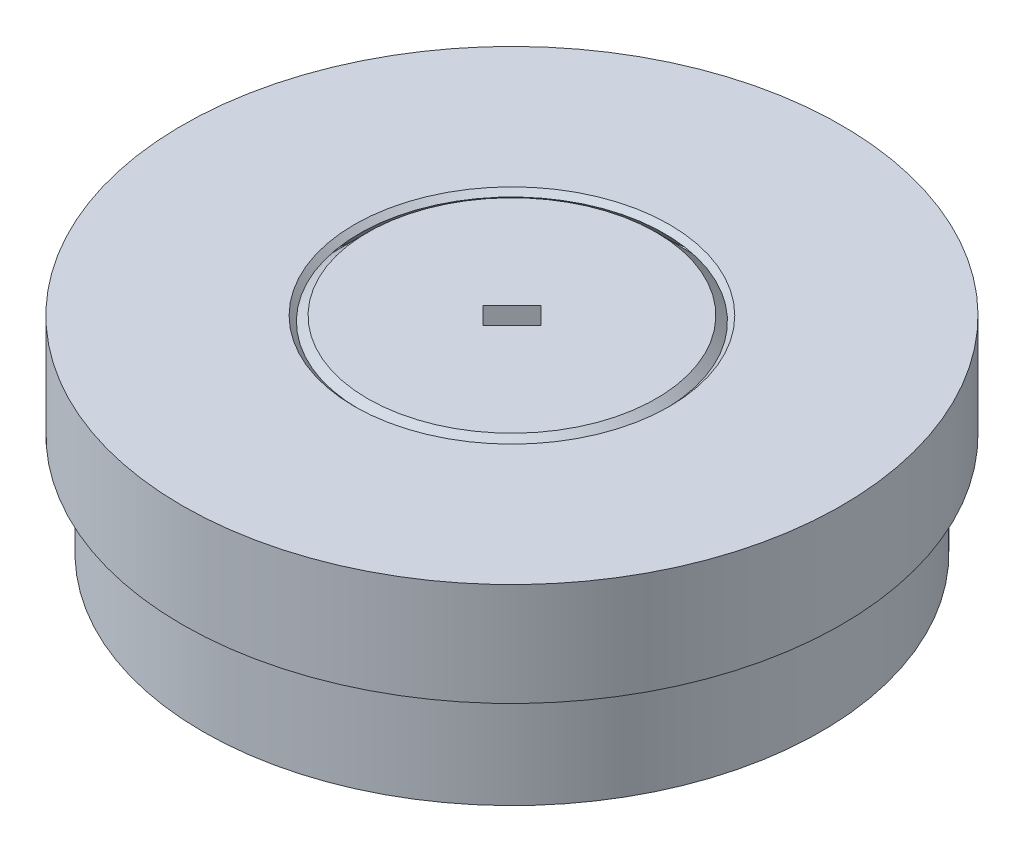
SolidWorks part; units mm, degrees
ref_plane "Front Plane" through (0, 0, 0) normal (0, 0, 1) x (1, 0, 0)
ref_plane "Top Plane" through (0, 0, 0) normal (0, 1, 0) x (1, 0, 0)
ref_plane "Right Plane" through (0, 0, 0) normal (1, 0, 0) x (0, 0, -1)
sketch "Sketch3" plane through (0, 0, 0) normal (0, 1, 0) x (1, 0, 0)
  line L0 (0, 0) -> (0, 14) construction
  line L1 (0, 11) -> (0, 14)
  line L2 (6.4656, 8.8992) -> (8.229, 11.3262)
  line L3 (10.4616, 3.3992) -> (13.3148, 4.3262)
  line L4 (10.4616, -3.3992) -> (13.3148, -4.3262)
  line L5 (6.4656, -8.8992) -> (8.229, -11.3262)
  line L6 (0, -11) -> (0, -14)
  line L7 (-6.4656, -8.8992) -> (-8.229, -11.3262)
  line L8 (-10.4616, -3.3992) -> (-13.3148, -4.3262)
  line L9 (-10.4616, 3.3992) -> (-13.3148, 4.3262)
  line L10 (-6.4656, 8.8992) -> (-8.229, 11.3262)
  line L12 (2, 2) -> (-2, 2)
  line L13 (2, 2) -> (2, -2)
  line L14 (2, -2) -> (-2, -2)
  line L15 (-2, 2) -> (-2, -2)
  line L16 (0, -2) -> (0, 2) construction
  line L17 (2, 0) -> (-2, 0) construction
  circle A0 centre (0, 0) radius 15
  circle A1 centre (0, 0) radius 14 construction
  spline S0 degree 4 poles (-0.6778, 10.6763) (-0.6286, 10.7014) (-0.5336, 10.7495) (-0.4182, 10.8106) (-0.084, 10.9641) (0.0577, 11.0264) (0.4379, 11.1818) (0.6637, 11.2619) (0.971, 11.3685) (1.234, 11.4472) (1.5272, 11.5305) (1.8056, 11.5989) (2.0959, 11.6642) (2.3817, 11.7192) (2.6725, 11.7684) (2.9623, 11.8092) (3.2542, 11.8431) (3.5945, 11.8737) (4.009, 11.8986) (4.4979, 11.9088) (4.9859, 11.897) (5.4262, 11.8684) (5.7898, 11.8338) (6.0839, 11.7981) (6.4416, 11.7478) (6.8131, 11.6815) (7.1561, 11.6125) (7.5364, 11.5205) (7.7792, 11.459) (8.1801, 11.3427) (8.3369, 11.2932) (8.7269, 11.165) (8.8594, 11.1137) (8.9726, 11.0725) (9.0307, 11.0511) knots 0 0 0 0 0 0.018755 0.037509 0.074516 0.103872 0.133229 0.162585 0.191942 0.221299 0.250655 0.280012 0.309368 0.338725 0.368082 0.397438 0.426795 0.456151 0.504872 0.563586 0.622299 0.651656 0.681012 0.710369 0.739725 0.798439 0.827795 0.857152 0.886508 0.915865 0.957933 0.978966 1 1 1 1 1 construction
  spline S1 degree 4 poles (0, 11) (0.0566, 11.0246) (0.1702, 11.0724) (0.4379, 11.1818) (0.6637, 11.2619) (0.971, 11.3685) (1.234, 11.4472) (1.5272, 11.5305) (1.8056, 11.5989) (2.0959, 11.6642) (2.3817, 11.7192) (2.6725, 11.7684) (2.9623, 11.8092) (3.2542, 11.8431) (3.5945, 11.8737) (4.009, 11.8986) (4.4979, 11.9088) (4.9859, 11.897) (5.4262, 11.8684) (5.7898, 11.8338) (6.0839, 11.7981) (6.4416, 11.7478) (6.8131, 11.6815) (7.1561, 11.6125) (7.5364, 11.5205) (7.7792, 11.459) (8.0505, 11.3803) (8.17, 11.3445) (8.229, 11.3262) knots 0.074516 0.074516 0.074516 0.074516 0.074516 0.103872 0.133229 0.162585 0.191942 0.221299 0.250655 0.280012 0.309368 0.338725 0.368082 0.397438 0.426795 0.456151 0.504872 0.563586 0.622299 0.651656 0.681012 0.710369 0.739725 0.798439 0.827795 0.857152 0.886508 0.915865 0.915865 0.915865 0.915865 0.915865
  spline S2 degree 4 poles (5.727, 9.0357) (5.7816, 9.0271) (5.8867, 9.0101) (6.016, 8.9918) (6.3766, 8.9195) (6.5279, 8.8866) (6.9268, 8.7889) (7.1565, 8.7209) (7.4678, 8.6266) (7.7268, 8.5357) (8.013, 8.4307) (8.2785, 8.3224) (8.5517, 8.2045) (8.8152, 8.0811) (9.0794, 7.95) (9.3378, 7.8126) (9.5939, 7.6685) (9.8872, 7.4932) (10.2371, 7.2697) (10.6387, 6.9906) (11.0265, 6.6943) (11.3659, 6.4123) (11.6398, 6.1706) (11.8567, 5.9689) (12.1165, 5.7179) (12.3781, 5.4459) (12.6151, 5.1885) (12.8687, 4.8905) (13.029, 4.698) (13.2848, 4.3683) (13.3827, 4.236) (13.6228, 3.9031) (13.6999, 3.7838) (13.7672, 3.6839) (13.8017, 3.6324) knots 0 0 0 0 0 0.018755 0.037509 0.074516 0.103872 0.133229 0.162585 0.191942 0.221299 0.250655 0.280012 0.309368 0.338725 0.368082 0.397438 0.426795 0.456151 0.504872 0.563586 0.622299 0.651656 0.681012 0.710369 0.739725 0.798439 0.827795 0.857152 0.886508 0.915865 0.957933 0.978966 1 1 1 1 1 construction
  spline S3 degree 4 poles (6.4656, 8.8992) (6.5259, 8.8858) (6.6459, 8.8577) (6.9268, 8.7889) (7.1565, 8.7209) (7.4678, 8.6266) (7.7268, 8.5357) (8.013, 8.4307) (8.2785, 8.3224) (8.5517, 8.2045) (8.8152, 8.0811) (9.0794, 7.95) (9.3378, 7.8126) (9.5939, 7.6685) (9.8872, 7.4932) (10.2371, 7.2697) (10.6387, 6.9906) (11.0265, 6.6943) (11.3659, 6.4123) (11.6398, 6.1706) (11.8567, 5.9689) (12.1165, 5.7179) (12.3781, 5.4459) (12.6151, 5.1885) (12.8687, 4.8905) (13.029, 4.698) (13.2021, 4.4749) (13.2778, 4.3756) (13.3148, 4.3262) knots 0.074516 0.074516 0.074516 0.074516 0.074516 0.103872 0.133229 0.162585 0.191942 0.221299 0.250655 0.280012 0.309368 0.338725 0.368082 0.397438 0.426795 0.456151 0.504872 0.563586 0.622299 0.651656 0.681012 0.710369 0.739725 0.798439 0.827795 0.857152 0.886508 0.915865 0.915865 0.915865 0.915865 0.915865
  spline S4 degree 4 poles (9.9443, 3.9438) (9.9834, 3.9047) (10.0585, 3.8292) (10.1522, 3.7384) (10.4015, 3.468) (10.5046, 3.3524) (10.7698, 3.0389) (10.9158, 2.8489) (11.1122, 2.5895) (11.2683, 2.3638) (11.4381, 2.1106) (11.5892, 1.867) (11.7409, 1.6111) (11.8816, 1.3563) (12.0183, 1.095) (12.1466, 0.8319) (12.2691, 0.5648) (12.4033, 0.2506) (12.5551, -0.1359) (12.7158, -0.5977) (12.8555, -1.0654) (12.9643, -1.493) (13.0438, -1.8496) (13.1007, -2.1403) (13.1634, -2.496) (13.2151, -2.8698) (13.2555, -3.2174) (13.2855, -3.6076) (13.3021, -3.8575) (13.3153, -4.2746) (13.3167, -4.4391) (13.3153, -4.8496) (13.3075, -4.9915) (13.3032, -5.1118) (13.3009, -5.1737) knots 0 0 0 0 0 0.018755 0.037509 0.074516 0.103872 0.133229 0.162585 0.191942 0.221299 0.250655 0.280012 0.309368 0.338725 0.368082 0.397438 0.426795 0.456151 0.504872 0.563586 0.622299 0.651656 0.681012 0.710369 0.739725 0.798439 0.827795 0.857152 0.886508 0.915865 0.957933 0.978966 1 1 1 1 1 construction
  spline S5 degree 4 poles (10.4616, 3.3992) (10.5025, 3.3529) (10.583, 3.2597) (10.7698, 3.0389) (10.9158, 2.8489) (11.1122, 2.5895) (11.2683, 2.3638) (11.4381, 2.1106) (11.5892, 1.867) (11.7409, 1.6111) (11.8816, 1.3563) (12.0183, 1.095) (12.1466, 0.8319) (12.2691, 0.5648) (12.4033, 0.2506) (12.5551, -0.1359) (12.7158, -0.5977) (12.8555, -1.0654) (12.9643, -1.493) (13.0438, -1.8496) (13.1007, -2.1403) (13.1634, -2.496) (13.2151, -2.8698) (13.2555, -3.2174) (13.2855, -3.6076) (13.3021, -3.8575) (13.311, -4.1398) (13.3139, -4.2645) (13.3148, -4.3262) knots 0.074516 0.074516 0.074516 0.074516 0.074516 0.103872 0.133229 0.162585 0.191942 0.221299 0.250655 0.280012 0.309368 0.338725 0.368082 0.397438 0.426795 0.456151 0.504872 0.563586 0.622299 0.651656 0.681012 0.710369 0.739725 0.798439 0.827795 0.857152 0.886508 0.915865 0.915865 0.915865 0.915865 0.915865
  spline S6 degree 4 poles (10.3632, -2.6545) (10.3719, -2.7091) (10.3882, -2.8143) (10.4107, -2.9429) (10.4535, -3.3082) (10.4689, -3.4622) (10.4992, -3.8718) (10.5056, -4.1113) (10.512, -4.4366) (10.5056, -4.711) (10.4942, -5.0156) (10.4732, -5.3015) (10.4456, -5.5978) (10.4097, -5.8866) (10.3666, -6.1783) (10.3158, -6.4665) (10.2579, -6.7546) (10.1818, -7.0878) (10.0774, -7.4896) (9.936, -7.9578) (9.774, -8.4182) (9.6108, -8.8281) (9.4655, -9.1633) (9.3407, -9.4319) (9.1823, -9.7566) (9.0044, -10.0894) (8.8328, -10.3943) (8.6277, -10.7276) (8.4943, -10.9395) (8.2597, -11.2848) (8.1642, -11.4187) (7.9218, -11.7499) (7.8321, -11.8601) (7.7579, -11.955) (7.7196, -12.0037) knots 0 0 0 0 0 0.018755 0.037509 0.074516 0.103872 0.133229 0.162585 0.191942 0.221299 0.250655 0.280012 0.309368 0.338725 0.368082 0.397438 0.426795 0.456151 0.504872 0.563586 0.622299 0.651656 0.681012 0.710369 0.739725 0.798439 0.827795 0.857152 0.886508 0.915865 0.957933 0.978966 1 1 1 1 1 construction
  spline S7 degree 4 poles (10.4616, -3.3992) (10.4675, -3.4606) (10.4779, -3.5834) (10.4992, -3.8718) (10.5056, -4.1113) (10.512, -4.4366) (10.5056, -4.711) (10.4942, -5.0156) (10.4732, -5.3015) (10.4456, -5.5978) (10.4097, -5.8866) (10.3666, -6.1783) (10.3158, -6.4665) (10.2579, -6.7546) (10.1818, -7.0878) (10.0774, -7.4896) (9.936, -7.9578) (9.774, -8.4182) (9.6108, -8.8281) (9.4655, -9.1633) (9.3407, -9.4319) (9.1823, -9.7566) (9.0044, -10.0894) (8.8328, -10.3943) (8.6277, -10.7276) (8.4943, -10.9395) (8.3355, -11.1732) (8.2645, -11.2758) (8.229, -11.3262) knots 0.074516 0.074516 0.074516 0.074516 0.074516 0.103872 0.133229 0.162585 0.191942 0.221299 0.250655 0.280012 0.309368 0.338725 0.368082 0.397438 0.426795 0.456151 0.504872 0.563586 0.622299 0.651656 0.681012 0.710369 0.739725 0.798439 0.827795 0.857152 0.886508 0.915865 0.915865 0.915865 0.915865 0.915865
  spline S8 degree 4 poles (6.8238, -8.2389) (6.7987, -8.2881) (6.75, -8.3829) (6.6926, -8.5001) (6.5125, -8.8208) (6.4344, -8.9545) (6.2182, -9.3037) (6.0826, -9.5012) (5.8967, -9.7681) (5.7302, -9.9863) (5.5419, -10.2261) (5.3569, -10.445) (5.1604, -10.6685) (4.9615, -10.881) (4.7552, -11.0917) (4.5447, -11.295) (4.3285, -11.4941) (4.0712, -11.7188) (3.7505, -11.9826) (3.3609, -12.2782) (2.9593, -12.5555) (2.5862, -12.7912) (2.2717, -12.9769) (2.0128, -13.1209) (1.6938, -13.2904) (1.3544, -13.4552) (1.0362, -13.601) (0.6745, -13.7501) (0.4419, -13.8431) (0.0492, -13.9845) (-0.1068, -14.0367) (-0.4976, -14.1622) (-0.6349, -14.1986) (-0.7507, -14.2318) (-0.8103, -14.2487) knots 0 0 0 0 0 0.018755 0.037509 0.074516 0.103872 0.133229 0.162585 0.191942 0.221299 0.250655 0.280012 0.309368 0.338725 0.368082 0.397438 0.426795 0.456151 0.504872 0.563586 0.622299 0.651656 0.681012 0.710369 0.739725 0.798439 0.827795 0.857152 0.886508 0.915865 0.957933 0.978966 1 1 1 1 1 construction
  spline S9 degree 4 poles (6.4656, -8.8992) (6.4343, -8.9523) (6.3705, -9.0578) (6.2182, -9.3037) (6.0826, -9.5012) (5.8967, -9.7681) (5.7302, -9.9863) (5.5419, -10.2261) (5.3569, -10.445) (5.1604, -10.6685) (4.9615, -10.881) (4.7552, -11.0917) (4.5447, -11.295) (4.3285, -11.4941) (4.0712, -11.7188) (3.7505, -11.9826) (3.3609, -12.2782) (2.9593, -12.5555) (2.5862, -12.7912) (2.2717, -12.9769) (2.0128, -13.1209) (1.6938, -13.2904) (1.3544, -13.4552) (1.0362, -13.601) (0.6745, -13.7501) (0.4419, -13.8431) (0.1762, -13.9388) (0.0584, -13.9801) (0, -14) knots 0.074516 0.074516 0.074516 0.074516 0.074516 0.103872 0.133229 0.162585 0.191942 0.221299 0.250655 0.280012 0.309368 0.338725 0.368082 0.397438 0.426795 0.456151 0.504872 0.563586 0.622299 0.651656 0.681012 0.710369 0.739725 0.798439 0.827795 0.857152 0.886508 0.915865 0.915865 0.915865 0.915865 0.915865
  spline S10 degree 4 poles (0.6778, -10.6763) (0.6286, -10.7014) (0.5336, -10.7495) (0.4182, -10.8106) (0.084, -10.9641) (-0.0577, -11.0264) (-0.4379, -11.1818) (-0.6637, -11.2619) (-0.971, -11.3685) (-1.234, -11.4472) (-1.5272, -11.5305) (-1.8056, -11.5989) (-2.0959, -11.6642) (-2.3817, -11.7192) (-2.6725, -11.7684) (-2.9623, -11.8092) (-3.2542, -11.8431) (-3.5945, -11.8737) (-4.009, -11.8986) (-4.4979, -11.9088) (-4.9859, -11.897) (-5.4262, -11.8684) (-5.7898, -11.8338) (-6.0839, -11.7981) (-6.4416, -11.7478) (-6.8131, -11.6815) (-7.1561, -11.6125) (-7.5364, -11.5205) (-7.7792, -11.459) (-8.1801, -11.3427) (-8.3369, -11.2932) (-8.7269, -11.165) (-8.8594, -11.1137) (-8.9726, -11.0725) (-9.0307, -11.0511) knots 0 0 0 0 0 0.018755 0.037509 0.074516 0.103872 0.133229 0.162585 0.191942 0.221299 0.250655 0.280012 0.309368 0.338725 0.368082 0.397438 0.426795 0.456151 0.504872 0.563586 0.622299 0.651656 0.681012 0.710369 0.739725 0.798439 0.827795 0.857152 0.886508 0.915865 0.957933 0.978966 1 1 1 1 1 construction
  spline S11 degree 4 poles (0, -11) (-0.0566, -11.0246) (-0.1702, -11.0724) (-0.4379, -11.1818) (-0.6637, -11.2619) (-0.971, -11.3685) (-1.234, -11.4472) (-1.5272, -11.5305) (-1.8056, -11.5989) (-2.0959, -11.6642) (-2.3817, -11.7192) (-2.6725, -11.7684) (-2.9623, -11.8092) (-3.2542, -11.8431) (-3.5945, -11.8737) (-4.009, -11.8986) (-4.4979, -11.9088) (-4.9859, -11.897) (-5.4262, -11.8684) (-5.7898, -11.8338) (-6.0839, -11.7981) (-6.4416, -11.7478) (-6.8131, -11.6815) (-7.1561, -11.6125) (-7.5364, -11.5205) (-7.7792, -11.459) (-8.0505, -11.3803) (-8.17, -11.3445) (-8.229, -11.3262) knots 0.074516 0.074516 0.074516 0.074516 0.074516 0.103872 0.133229 0.162585 0.191942 0.221299 0.250655 0.280012 0.309368 0.338725 0.368082 0.397438 0.426795 0.456151 0.504872 0.563586 0.622299 0.651656 0.681012 0.710369 0.739725 0.798439 0.827795 0.857152 0.886508 0.915865 0.915865 0.915865 0.915865 0.915865
  spline S12 degree 4 poles (-5.727, -9.0357) (-5.7816, -9.0271) (-5.8867, -9.0101) (-6.016, -8.9918) (-6.3766, -8.9195) (-6.5279, -8.8866) (-6.9268, -8.7889) (-7.1565, -8.7209) (-7.4678, -8.6266) (-7.7268, -8.5357) (-8.013, -8.4307) (-8.2785, -8.3224) (-8.5517, -8.2045) (-8.8152, -8.0811) (-9.0794, -7.95) (-9.3378, -7.8126) (-9.5939, -7.6685) (-9.8872, -7.4932) (-10.2371, -7.2697) (-10.6387, -6.9906) (-11.0265, -6.6943) (-11.3659, -6.4123) (-11.6398, -6.1706) (-11.8567, -5.9689) (-12.1165, -5.7179) (-12.3781, -5.4459) (-12.6151, -5.1885) (-12.8687, -4.8905) (-13.029, -4.698) (-13.2848, -4.3683) (-13.3827, -4.236) (-13.6228, -3.9031) (-13.6999, -3.7838) (-13.7672, -3.6839) (-13.8017, -3.6324) knots 0 0 0 0 0 0.018755 0.037509 0.074516 0.103872 0.133229 0.162585 0.191942 0.221299 0.250655 0.280012 0.309368 0.338725 0.368082 0.397438 0.426795 0.456151 0.504872 0.563586 0.622299 0.651656 0.681012 0.710369 0.739725 0.798439 0.827795 0.857152 0.886508 0.915865 0.957933 0.978966 1 1 1 1 1 construction
  spline S13 degree 4 poles (-6.4656, -8.8992) (-6.5259, -8.8858) (-6.6459, -8.8577) (-6.9268, -8.7889) (-7.1565, -8.7209) (-7.4678, -8.6266) (-7.7268, -8.5357) (-8.013, -8.4307) (-8.2785, -8.3224) (-8.5517, -8.2045) (-8.8152, -8.0811) (-9.0794, -7.95) (-9.3378, -7.8126) (-9.5939, -7.6685) (-9.8872, -7.4932) (-10.2371, -7.2697) (-10.6387, -6.9906) (-11.0265, -6.6943) (-11.3659, -6.4123) (-11.6398, -6.1706) (-11.8567, -5.9689) (-12.1165, -5.7179) (-12.3781, -5.4459) (-12.6151, -5.1885) (-12.8687, -4.8905) (-13.029, -4.698) (-13.2021, -4.4749) (-13.2778, -4.3756) (-13.3148, -4.3262) knots 0.074516 0.074516 0.074516 0.074516 0.074516 0.103872 0.133229 0.162585 0.191942 0.221299 0.250655 0.280012 0.309368 0.338725 0.368082 0.397438 0.426795 0.456151 0.504872 0.563586 0.622299 0.651656 0.681012 0.710369 0.739725 0.798439 0.827795 0.857152 0.886508 0.915865 0.915865 0.915865 0.915865 0.915865
  spline S14 degree 4 poles (-9.9443, -3.9438) (-9.9834, -3.9047) (-10.0585, -3.8292) (-10.1522, -3.7384) (-10.4015, -3.468) (-10.5046, -3.3524) (-10.7698, -3.0389) (-10.9158, -2.8489) (-11.1122, -2.5895) (-11.2683, -2.3638) (-11.4381, -2.1106) (-11.5892, -1.867) (-11.7409, -1.6111) (-11.8816, -1.3563) (-12.0183, -1.095) (-12.1466, -0.8319) (-12.2691, -0.5648) (-12.4033, -0.2506) (-12.5551, 0.1359) (-12.7158, 0.5977) (-12.8555, 1.0654) (-12.9643, 1.493) (-13.0438, 1.8496) (-13.1007, 2.1403) (-13.1634, 2.496) (-13.2151, 2.8698) (-13.2555, 3.2174) (-13.2855, 3.6076) (-13.3021, 3.8575) (-13.3153, 4.2746) (-13.3167, 4.4391) (-13.3153, 4.8496) (-13.3075, 4.9915) (-13.3032, 5.1118) (-13.3009, 5.1737) knots 0 0 0 0 0 0.018755 0.037509 0.074516 0.103872 0.133229 0.162585 0.191942 0.221299 0.250655 0.280012 0.309368 0.338725 0.368082 0.397438 0.426795 0.456151 0.504872 0.563586 0.622299 0.651656 0.681012 0.710369 0.739725 0.798439 0.827795 0.857152 0.886508 0.915865 0.957933 0.978966 1 1 1 1 1 construction
  spline S15 degree 4 poles (-10.4616, -3.3992) (-10.5025, -3.3529) (-10.583, -3.2597) (-10.7698, -3.0389) (-10.9158, -2.8489) (-11.1122, -2.5895) (-11.2683, -2.3638) (-11.4381, -2.1106) (-11.5892, -1.867) (-11.7409, -1.6111) (-11.8816, -1.3563) (-12.0183, -1.095) (-12.1466, -0.8319) (-12.2691, -0.5648) (-12.4033, -0.2506) (-12.5551, 0.1359) (-12.7158, 0.5977) (-12.8555, 1.0654) (-12.9643, 1.493) (-13.0438, 1.8496) (-13.1007, 2.1403) (-13.1634, 2.496) (-13.2151, 2.8698) (-13.2555, 3.2174) (-13.2855, 3.6076) (-13.3021, 3.8575) (-13.311, 4.1398) (-13.3139, 4.2645) (-13.3148, 4.3262) knots 0.074516 0.074516 0.074516 0.074516 0.074516 0.103872 0.133229 0.162585 0.191942 0.221299 0.250655 0.280012 0.309368 0.338725 0.368082 0.397438 0.426795 0.456151 0.504872 0.563586 0.622299 0.651656 0.681012 0.710369 0.739725 0.798439 0.827795 0.857152 0.886508 0.915865 0.915865 0.915865 0.915865 0.915865
  spline S16 degree 4 poles (-10.3632, 2.6545) (-10.3719, 2.7091) (-10.3882, 2.8143) (-10.4107, 2.9429) (-10.4535, 3.3082) (-10.4689, 3.4622) (-10.4992, 3.8718) (-10.5056, 4.1113) (-10.512, 4.4366) (-10.5056, 4.711) (-10.4942, 5.0156) (-10.4732, 5.3015) (-10.4456, 5.5978) (-10.4097, 5.8866) (-10.3666, 6.1783) (-10.3158, 6.4665) (-10.2579, 6.7546) (-10.1818, 7.0878) (-10.0774, 7.4896) (-9.936, 7.9578) (-9.774, 8.4182) (-9.6108, 8.8281) (-9.4655, 9.1633) (-9.3407, 9.4319) (-9.1823, 9.7566) (-9.0044, 10.0894) (-8.8328, 10.3943) (-8.6277, 10.7276) (-8.4943, 10.9395) (-8.2597, 11.2848) (-8.1642, 11.4187) (-7.9218, 11.7499) (-7.8321, 11.8601) (-7.7579, 11.955) (-7.7196, 12.0037) knots 0 0 0 0 0 0.018755 0.037509 0.074516 0.103872 0.133229 0.162585 0.191942 0.221299 0.250655 0.280012 0.309368 0.338725 0.368082 0.397438 0.426795 0.456151 0.504872 0.563586 0.622299 0.651656 0.681012 0.710369 0.739725 0.798439 0.827795 0.857152 0.886508 0.915865 0.957933 0.978966 1 1 1 1 1 construction
  spline S17 degree 4 poles (-10.4616, 3.3992) (-10.4675, 3.4606) (-10.4779, 3.5834) (-10.4992, 3.8718) (-10.5056, 4.1113) (-10.512, 4.4366) (-10.5056, 4.711) (-10.4942, 5.0156) (-10.4732, 5.3015) (-10.4456, 5.5978) (-10.4097, 5.8866) (-10.3666, 6.1783) (-10.3158, 6.4665) (-10.2579, 6.7546) (-10.1818, 7.0878) (-10.0774, 7.4896) (-9.936, 7.9578) (-9.774, 8.4182) (-9.6108, 8.8281) (-9.4655, 9.1633) (-9.3407, 9.4319) (-9.1823, 9.7566) (-9.0044, 10.0894) (-8.8328, 10.3943) (-8.6277, 10.7276) (-8.4943, 10.9395) (-8.3355, 11.1732) (-8.2645, 11.2758) (-8.229, 11.3262) knots 0.074516 0.074516 0.074516 0.074516 0.074516 0.103872 0.133229 0.162585 0.191942 0.221299 0.250655 0.280012 0.309368 0.338725 0.368082 0.397438 0.426795 0.456151 0.504872 0.563586 0.622299 0.651656 0.681012 0.710369 0.739725 0.798439 0.827795 0.857152 0.886508 0.915865 0.915865 0.915865 0.915865 0.915865
  spline S18 degree 4 poles (-6.8238, 8.2389) (-6.7987, 8.2881) (-6.75, 8.3829) (-6.6926, 8.5001) (-6.5125, 8.8208) (-6.4344, 8.9545) (-6.2182, 9.3037) (-6.0826, 9.5012) (-5.8967, 9.7681) (-5.7302, 9.9863) (-5.5419, 10.2261) (-5.3569, 10.445) (-5.1604, 10.6685) (-4.9615, 10.881) (-4.7552, 11.0917) (-4.5447, 11.295) (-4.3285, 11.4941) (-4.0712, 11.7188) (-3.7505, 11.9826) (-3.3609, 12.2782) (-2.9593, 12.5555) (-2.5862, 12.7912) (-2.2717, 12.9769) (-2.0128, 13.1209) (-1.6938, 13.2904) (-1.3544, 13.4552) (-1.0362, 13.601) (-0.6745, 13.7501) (-0.4419, 13.8431) (-0.0492, 13.9845) (0.1068, 14.0367) (0.4976, 14.1622) (0.6349, 14.1986) (0.7507, 14.2318) (0.8103, 14.2487) knots 0 0 0 0 0 0.018755 0.037509 0.074516 0.103872 0.133229 0.162585 0.191942 0.221299 0.250655 0.280012 0.309368 0.338725 0.368082 0.397438 0.426795 0.456151 0.504872 0.563586 0.622299 0.651656 0.681012 0.710369 0.739725 0.798439 0.827795 0.857152 0.886508 0.915865 0.957933 0.978966 1 1 1 1 1 construction
  spline S19 degree 4 poles (-6.4656, 8.8992) (-6.4343, 8.9523) (-6.3705, 9.0578) (-6.2182, 9.3037) (-6.0826, 9.5012) (-5.8967, 9.7681) (-5.7302, 9.9863) (-5.5419, 10.2261) (-5.3569, 10.445) (-5.1604, 10.6685) (-4.9615, 10.881) (-4.7552, 11.0917) (-4.5447, 11.295) (-4.3285, 11.4941) (-4.0712, 11.7188) (-3.7505, 11.9826) (-3.3609, 12.2782) (-2.9593, 12.5555) (-2.5862, 12.7912) (-2.2717, 12.9769) (-2.0128, 13.1209) (-1.6938, 13.2904) (-1.3544, 13.4552) (-1.0362, 13.601) (-0.6745, 13.7501) (-0.4419, 13.8431) (-0.1762, 13.9388) (-0.0584, 13.9801) (0, 14) knots 0.074516 0.074516 0.074516 0.074516 0.074516 0.103872 0.133229 0.162585 0.191942 0.221299 0.250655 0.280012 0.309368 0.338725 0.368082 0.397438 0.426795 0.456151 0.504872 0.563586 0.622299 0.651656 0.681012 0.710369 0.739725 0.798439 0.827795 0.857152 0.886508 0.915865 0.915865 0.915865 0.915865 0.915865
  point P57 (0, 0)
  dimension "D1" = 30
  dimension "D2" = 28
  dimension "D3" = 10
  dimension "D4" = 4
  dimension "D5" = 4
extrude "Boss-Extrude1" add sketch "Sketch3" along normal blind 3 contours A0 L10 S19 L1 S1 L2 S3 L3 S5 L4 S7 L5 S9 L6 S11 L7 S13 L8 S15 L9 S17 | L13 L12 L15 L14 region at (-14.5757, 0, 0)
sketch "Sketch5" plane through (0, 0, 0) normal (1, 0, 0) x (0, 0, -1)
  line L0 (-2, 0) -> (-2, 3) construction
  line L1 (-2, 3) -> (2, 3) construction
  line L2 (2, 3) -> (2, 0) construction
  line L3 (2, 0) -> (-2, 0) construction
  line L4 (-2, 3) -> (2, 0) construction
  line L5 (-2, 0) -> (2, 3) construction
  line L6 (15, 0) -> (15, 3) construction
  line L7 (-15, 3) -> (15, 3) construction
  line L8 (-15, 3) -> (-15, 10) construction
  line L9 (-15, 10) -> (15, 10) construction
  line L10 (15, 3) -> (15, 10) construction
  line L11 (0, 10) -> (0, 3) construction
  line L12 (-15, 6.5) -> (15, 6.5) construction
  line L13 (15, 5) -> (16, 5) construction
  line L14 (-15, 10) -> (-16, 10) construction
  line L15 (-15, 10) -> (-15, 5) construction
  line L16 (-15, 5) -> (-16, 5) construction
  line L17 (-16, 10) -> (-16, 5) construction
  line L18 (-15.5, 5) -> (-15.5, 10) construction
  line L19 (-15, 7.5) -> (-16, 7.5) construction
  line L20 (15, 10) -> (16, 10) construction
  line L21 (16, 10) -> (16, 5) construction
  line L22 (-7, 10) -> (-9.5, 7.5)
  line L23 (7, 3) -> (-7, 3) construction
  line L24 (7, 3) -> (7, 10) construction
  line L25 (7, 10) -> (-7, 10) construction
  line L26 (-7, 3) -> (-7, 10) construction
  line L27 (0, 10) -> (0, 3) construction
  line L28 (7, 6.5) -> (-7, 6.5) construction
  line L29 (-7, 10) -> (7, 10) construction
  line L30 (-7, 10) -> (-7, 5) construction
  line L31 (-7, 5) -> (7, 5) construction
  line L32 (7, 10) -> (7, 5) construction
  line L33 (0, 5) -> (0, 10) construction
  line L34 (-7, 7.5) -> (7, 7.5) construction
  line L35 (7.15, 5) -> (-7.15, 5) construction
  line L36 (7.15, 5) -> (7.15, 10) construction
  line L37 (7.15, 10) -> (-7.15, 10) construction
  line L38 (-7.15, 5) -> (-7.15, 10) construction
  line L39 (0, 10) -> (0, 5) construction
  line L40 (7.15, 7.5) -> (-7.15, 7.5) construction
  line L41 (-9.5, 7.5) -> (-7, 5)
  line L42 (-7.15, 10) -> (-9.65, 7.5)
  line L43 (-9.65, 7.5) -> (-7.15, 5)
  line L44 (-7, 10) -> (0, 10)
  line L45 (0, 10) -> (0, 3)
  line L48 (-7, 5) -> (-7, 3)
  line L52 (-7.15, 5) -> (-9.65, 5)
  line L53 (-9.65, 5) -> (-9.65, 3)
  line L54 (-9.65, 3) -> (-15, 3)
  line L55 (-15, 3) -> (-15, 5)
  line L56 (-15, 5) -> (-16, 5)
  line L57 (-16, 5) -> (-16, 10)
  line L58 (-16, 10) -> (-7.15, 10)
  line L59 (0, 3) -> (-7, 3)
  point P20 (0, 6.5)
  point P27 (0, 7.5)
  point P289 (-15.5, 7.5)
  point P440 (0, 6.5)
  point P493 (0, 7.5)
  dimension "D1" = 7
  dimension "D2" = 5
  dimension "D3" = 1
  dimension "D4" = 14
  dimension "D5" = 5
  dimension "D6" = 0.15
  dimension "D7" = 90
  dimension "D8" = 90
  dimension "D9" = 2.5
revolve "Revolve1" add sketch "Sketch5" angle 360 about L45
fillet "Fillet2" radius 0.5 1 edges at (0, 3, 9.65)
fillet "Fillet3" radius 0.5 1 edges at (0, 3, 7)
chamfer "Chamfer1" distance 0.5 angle 45 4 edges at (2, 0, 0) (0, 0, -2) (-2, 0, 0) (0, 0, 2)
chamfer "Chamfer2" distance 0.5 angle 45 1 edges at (0, 10, 7.15) first distance on face at (0, 10, 16)
sketch "Sketch6" plane through (0, 0, 0) normal (0, -1, 0) x (1, 0, 0)
  line L0 (1.5, -1.5) -> (-1.5, 1.5) construction
  line L1 (-0.2828, 1.1314) -> (1.1314, -0.2828)
  line L2 (-0.2828, 1.1314) -> (-1.1314, 0.2828)
  line L3 (1.1314, -0.2828) -> (0.2828, -1.1314)
  line L4 (-1.1314, 0.2828) -> (0.2828, -1.1314)
  line L5 (-0.2828, 1.1314) -> (0.2828, -1.1314) construction
  line L6 (1.1314, -0.2828) -> (-1.1314, 0.2828) construction
  point P5 (0, 0)
  dimension "D1" = 1.2
  dimension "D2" = 2
extrude "Cut-Extrude1" cut sketch "Sketch6" against normal through all
